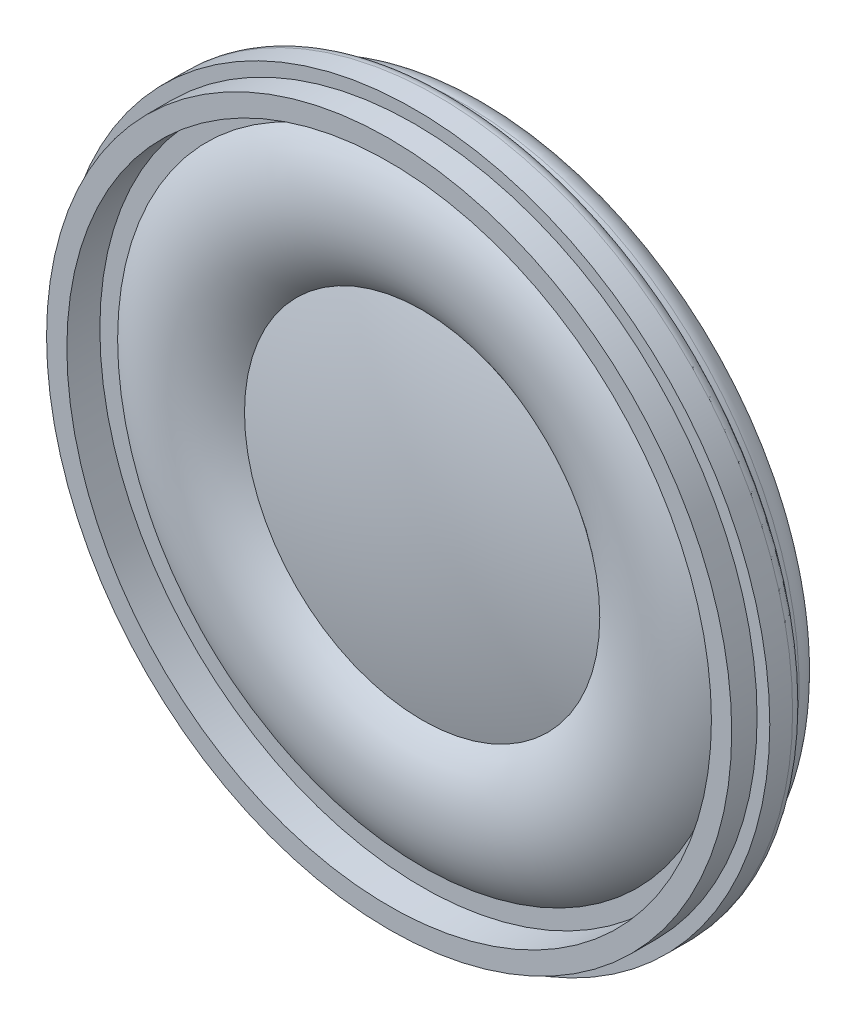
SolidWorks part; units mm, degrees
material "ABS"
ref_plane "Спереди" through (0, 0, 0) normal (0, 0, 1) x (1, 0, 0)
ref_plane "Сверху" through (0, 0, 0) normal (0, 1, 0) x (1, 0, 0)
ref_plane "Справа" through (0, 0, 0) normal (1, 0, 0) x (0, 0, -1)
ref_axis "Ось1" through (0, 0, 50) along (0, 0, -1)
sketch "Эскиз1" plane through (0, 0, 0) normal (0, 1, 0) x (1, 0, 0)
  line L0 (0, 0) -> (7.5, 0)
  line L1 (8, -0.5) -> (8, -1.5)
  line L2 (8, -1.5) -> (12.25, -1.5)
  line L3 (13.25, -2.5) -> (13.25, -3)
  line L4 (13.25, -3) -> (13.5, -3)
  line L5 (14, -3.5) -> (14, -4.4)
  line L6 (14, -4.4) -> (13.5, -4.4)
  line L7 (13.5, -4.4) -> (13.5, -5.4)
  line L8 (13.5, -5.4) -> (12.7, -5.4)
  line L9 (12.7, -5.4) -> (12.7, -4.1)
  line L10 (12.7, -4.1) -> (12, -4.1)
  line L11 (0, 0) -> (0, -5)
  line L12 (0, -5) -> (11.3788, -5) construction
  arc A0 (0, -5) -> (7, -4.1) centre (0, 22.6722) ccw
  arc A1 (7, -4.1) -> (12, -4.1) centre (9.5, -1.0778) ccw
  arc A2 (13.25, -2.5) -> (12.25, -1.5) centre (12.25, -2.5) ccw
  arc A3 (14, -3.5) -> (13.5, -3) centre (13.5, -3.5) ccw
  arc A4 (8, -0.5) -> (7.5, 0) centre (7.5, -0.5) ccw
  point P19 (13.25, -1.5)
  point P22 (14, -3)
  point P25 (8, 0)
  dimension "D1" = 14
  dimension "D12" = 1
  dimension "D15" = 12
  dimension "D16" = 0.5
  dimension "D17" = 0.5
  dimension "D2" = 8
  dimension "D3" = 1.5
  dimension "D4" = 13.25
  dimension "D5" = 1.5
  dimension "D6" = 1.4
  dimension "D7" = 1
  dimension "D8" = 13.5
  dimension "D9" = 0.8
  dimension "D10" = 1.3
  dimension "D11" = 5.4
  dimension "D13" = 7
  dimension "D14" = 5
revolve "Повернуть2" add sketch "Эскиз1" angle 360 about L11
sketch "Эскиз2" plane through (0, 0, 1.5) normal (0, 0, -1) x (-1, 0, 0)
  line L0 (-5.5645, 6.5899) -> (-7.5, 8.882)
  line L1 (5.5645, 6.5899) -> (7.5, 8.882)
  line L2 (0, 0) -> (-5.5645, 6.5899) construction
  line L3 (0, 0) -> (5.5645, 6.5899) construction
  line L4 (0, 8.625) -> (0, 11.625) construction
  line L5 (0, 8) -> (0, 12.25) construction
  arc A0 (5.5645, 6.5899) -> (-5.5645, 6.5899) centre (0, 0) ccw
  arc A1 (7.5, 8.882) -> (-7.5, 8.882) centre (0, 0) ccw
  circle A2 centre (0, 0) radius 8 construction
  circle A4 centre (0, 0) radius 12.25 construction
  point P11 (0, 10.125)
  point P12 (0, 10.125)
  point P13 (0, 12.25)
  dimension "D1" = 3
  dimension "D2" = 15
extrude "Бобышка-Вытянуть2" add sketch "Эскиз2" along normal blind 0.4
